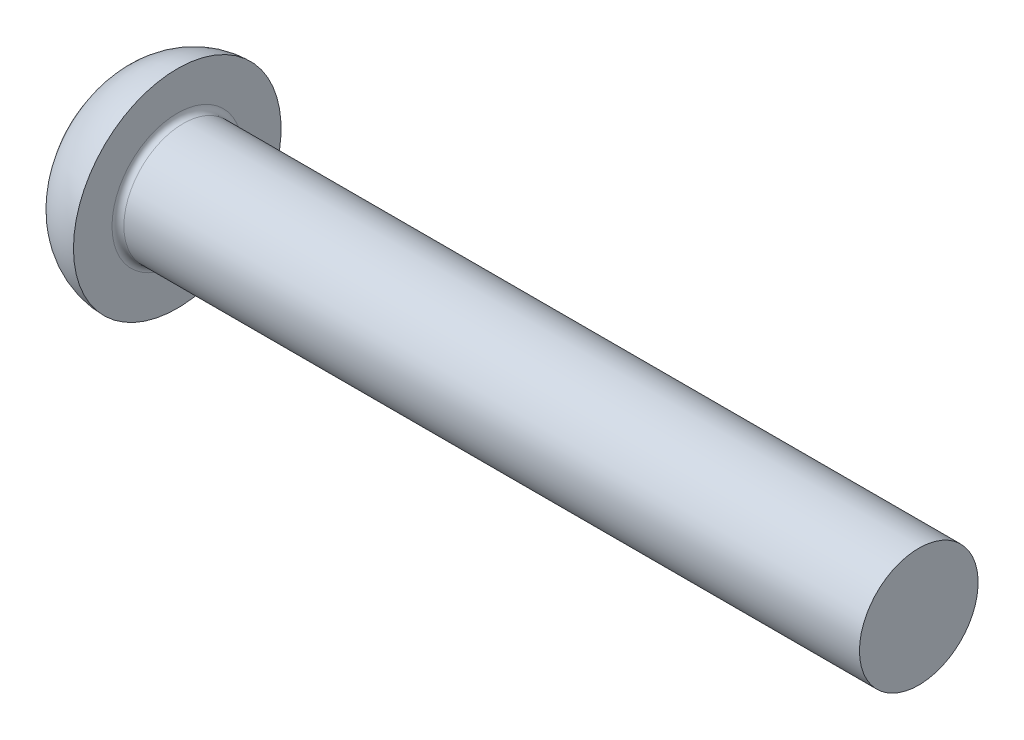
SolidWorks part; units mm, degrees
ref_plane "Front Plane" through (0, 0, 0) normal (0, 0, 1) x (1, 0, 0)
ref_plane "Top Plane" through (0, 0, 0) normal (0, 1, 0) x (1, 0, 0)
ref_plane "Right Plane" through (0, 0, 0) normal (1, 0, 0) x (0, 0, -1)
sketch "BodySke" plane through (0, 0, 0) normal (0, 0, 1) x (1, 0, 0)
  line L0 (0, 0) -> (111.3824, 0) construction
  line L1 (0, 0) -> (0, 8) construction
  line L2 (5.4, 4) -> (5.4, 7)
  line L4 (5.4, 4) -> (55.4, 4)
  line L5 (55.4, 4) -> (55.4, 0)
  line L6 (6.65, 7.824) -> (6.65, -6.8939) construction
  line L7 (0, 0) -> (55.4, 0)
  line L8 (25.4, 8.824) -> (25.4, -4.958) construction
  arc A0 (5.4, 7) -> (1.888, 5.306) centre (5.4541, 2.4003) ccw
  arc A1 (1.888, 5.306) -> (0, 0) centre (8.4, 0) ccw
  point P10 (55.4, 3.4455)
  dimension "Thread_minor" = 6.891
  dimension "Head_height" = 5.4
  dimension "Advance" = 1.25
  dimension "Length" = 50
  dimension "Head_dia" = 14
revolve "BaseBody" add sketch "BodySke" angle 360 about L0
cosmetic thread "ThreadCosmetic" [suppressed] parameters "Thread_minor"=6.891
fillet "Fillet1" radius 0.4 1 edges at (5.4, 0, 4)
ref_plane "Plane1" through (4.26, 0, 0) normal (1, 0, 0) x (0, 0, -1)
sketch "RecSkeTop" plane through (0, 0, 0) normal (1, 0, 0) x (0, 0, -1)
  line L1 (-0.847, 3.85) -> (0.847, 3.85)
  line L2 (-0.847, 3.85) -> (-0.847, -3.85)
  line L3 (-0.847, -3.85) -> (0.847, -3.85)
  line L4 (0.847, 3.85) -> (0.847, -3.85)
  dimension "D1" = 3.85
  dimension "D2" = 1.694
  dimension "D3" = 0.847
sketch "RecSkeBot" plane through (4.26, 0, 0) normal (1, 0, 0) x (0, 0, -1)
  line L0 (-0.847, 3.85) -> (-0.847, -3.85) construction
  line L1 (-0.847, 1.726) -> (0.847, 1.726)
  line L2 (-0.847, 1.726) -> (-0.847, -1.726)
  line L3 (-0.847, -1.726) -> (0.847, -1.726)
  line L4 (0.847, 1.726) -> (0.847, -1.726)
  line L5 (0.847, 3.85) -> (0.847, -3.85) construction
  dimension "D1" = 3.4521
  dimension "D2" = 1.726
loft "Recess" cut profiles "RecSkeTop", "RecSkeBot" connector at (0, -3.85, 0.847) connector at (4.26, -1.726, 0.847)
pattern_circular "RecPat" count 2 every 90 about axis through (0, 0, 0) along (1, 0, 0) of "Recess"
sketch "RecCorSke" plane through (0, 0, 0) normal (0, 0, 1) x (1, 0, 0)
  line L0 (0, 0) -> (57.5987, 0) construction
  line L1 (0, 0) -> (0, 1.8634)
  line L3 (0, 1.8634) -> (4.26, 1.5655)
  line L4 (4.26, 1.5655) -> (4.7687, 0)
  line L5 (4.7687, 0) -> (0, 0)
  dimension "D1" = 18
  dimension "D2" = 4.26
  dimension "D3" = 1.8634
  dimension "D4" = 4
revolve "RecessCore" cut sketch "RecCorSke" angle 360 about L0
sketch "ThdSchSke" plane through (0, 0, 0) normal (0, 0, 1) x (1, 0, 0)
  line L0 (0, 0) -> (55.1256, 0) construction
  line L1 (0, 0) -> (111.3824, 0) construction
  line L2 (55.0799, 4) -> (55.0799, 4.6403)
  line L3 (55.0799, 4.6403) -> (55.7201, 4.6403)
  line L4 (55.7201, 4.6403) -> (55.7201, 4)
  line L5 (55.7201, 4) -> (55.4, 3.4455)
  line L6 (55.4, 3.4455) -> (55.0799, 4)
  line L7 (5.4, 4) -> (55.4, 4) construction
  line L13 (55.4, 4) -> (55.4, 0) construction
revolve "ThreadSchematic" [suppressed] cut sketch "ThdSchSke" angle 360 about L0
pattern_linear "ThdSchPat" [suppressed] count 24 along (-1, 0, 0) of bodies 103
equation "\"Thread_minor@ThreadCosmetic\" = \"Thread_minor@BodySke\""
equation "\"D1@RecSkeTop\" = \"Cross_dia@RecSkeTop\" / 2"
equation "\"D2@RecSkeTop\" = \"Cross_dia@RecSkeTop\" * 0.22"
equation "\"D3@RecSkeTop\" = \"D2@RecSkeTop\" / 2"
equation "\"D1@RecSkeBot\" = \"Cross_dia@RecSkeTop\" - 2 * \"Cross_depth@Plane1\" *  tan( 26.5 * 0.017453292 ) "
equation "\"D2@RecSkeBot\" = \"D1@RecSkeBot\" / 2"
equation "\"D2@RecCorSke\" = \"Cross_depth@Plane1\""
equation "\"D3@RecCorSke\" = \"D2@RecSkeTop\" * 1.1"
equation "\"Advance@ThdSchPat\" = \"Advance@BodySke\""
equation "\"D1@ThdSchPat\" =  int( \"Thread_length@BodySke\" / \"Advance@ThdSchPat\" ) "
